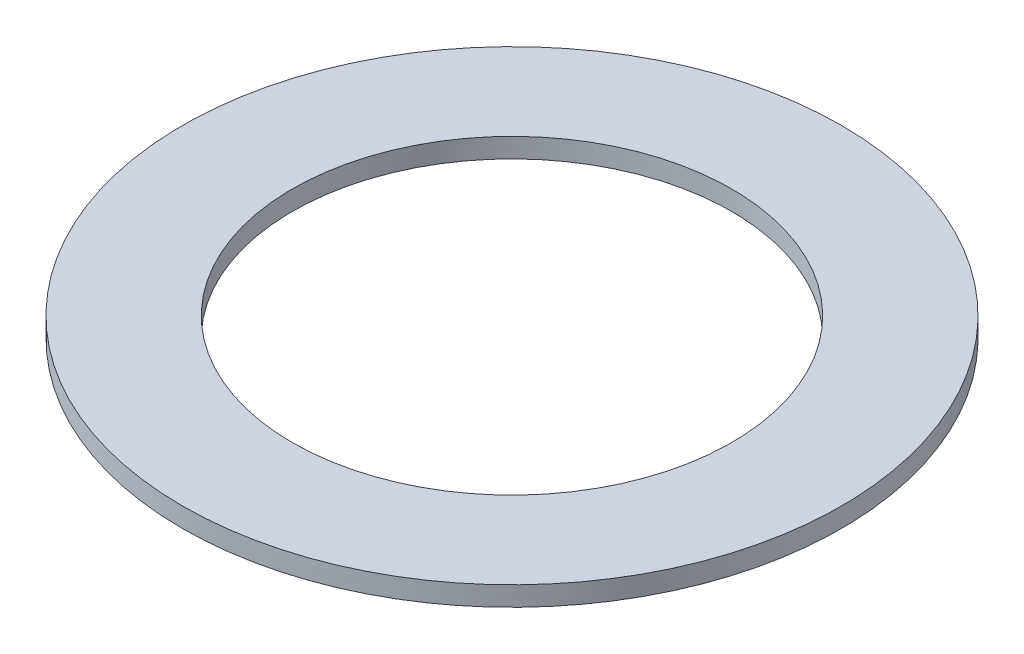
SolidWorks part; units mm, degrees
ref_plane "Front Plane" through (0, 0, 0) normal (0, 0, 1) x (1, 0, 0)
ref_plane "Top Plane" through (0, 0, 0) normal (0, 1, 0) x (1, 0, 0)
ref_plane "Right Plane" through (0, 0, 0) normal (1, 0, 0) x (0, 0, -1)
sketch "Sketch1" plane through (0, 0, 0) normal (0, 1, 0) x (1, 0, 0)
  circle A0 centre (0, 0) radius 67.5
  dimension "FLANGE_OD" = 135
extrude "Boss-Extrude1" add sketch "Sketch1" along normal blind 4
sketch "Sketch2" plane through (0, 0, 0) normal (0, 1, 0) x (1, 0, 0)
  circle A0 centre (0, 0) radius 45
  dimension "BORE_D" = 90
extrude "Cut-Extrude1" cut sketch "Sketch2" along normal through all
sketch "Sketch3" plane through (0, 4, 0) normal (0, 1, 0) x (1, 0, 0)
  circle A0 centre (0, 0) radius 27.0423 construction
  circle A1 centre (-27.0423, 0) radius 2.4061
  dimension "BOLT_D" = 4.8122
  dimension "BOLT_PCD" = 54.0846
extrude "Cut-Extrude2" cut sketch "Sketch3" against normal blind 2.8281 rebuild error yes
pattern_circular "CirPattern1" count 4 over 360 rebuild error yes
